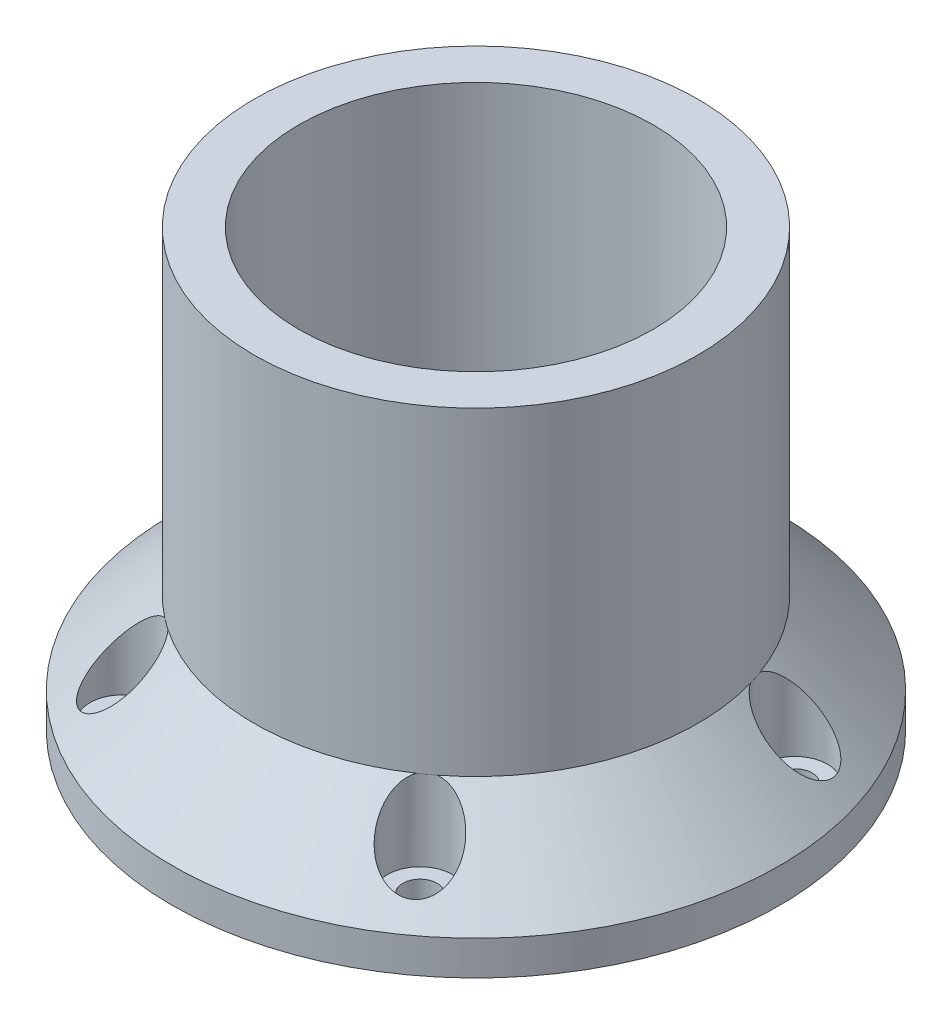
SolidWorks part; units mm, degrees
ref_plane "Front Plane" through (0, 0, 0) normal (0, 0, 1) x (1, 0, 0)
ref_plane "Top Plane" through (0, 0, 0) normal (0, 1, 0) x (1, 0, 0)
ref_plane "Right Plane" through (0, 0, 0) normal (1, 0, 0) x (0, 0, -1)
sketch "Sketch1" plane through (0, 0, 0) normal (0, 1, 0) x (1, 0, 0)
  circle A0 centre (0, 0) radius 25 construction
  circle A1 centre (0, 25) radius 1.7
  circle A2 centre (23.7764, 7.7254) radius 1.7
  circle A3 centre (14.6946, -20.2254) radius 1.7
  circle A4 centre (-14.6946, -20.2254) radius 1.7
  circle A5 centre (-23.7764, 7.7254) radius 1.7
  circle A6 centre (0, 0) radius 30
  circle A7 centre (0, 0) radius 17.5
  point P16 (0, 0)
  dimension "D1" = 50
  dimension "D2" = 3.4
  dimension "D4" = 60
  dimension "D5" = 35
  dimension "D3" = 5
extrude "Boss-Extrude1" add sketch "Sketch1" along normal blind 3
sketch "Sketch2" plane through (0, 3, 0) normal (0, 1, 0) x (1, 0, 0)
  circle A0 centre (0, 25) radius 3.1 construction
  circle A1 centre (0, 0) radius 21.9
  circle A2 centre (0, 0) radius 17.5 construction
  circle A3 centre (0, 0) radius 17.5
  dimension "D1" = 6.2
extrude "Boss-Extrude2" add sketch "Sketch2" along normal blind 40
chamfer "Chamfer1" distance 8.5 angle 45 1 edges at (0, 3, 21.9)
ref_plane "Plane1" through (0, 11.5, 0) normal (0, -1, 0) x (-1, 0, 0)
sketch "Sketch3" plane through (0, 11.5, 0) normal (0, -1, 0) x (-1, 0, 0)
  circle A0 centre (0, 25) radius 1.7 construction
  circle A1 centre (0, 25) radius 1.7
  circle A2 centre (0, 25) radius 3.2
  circle A3 centre (23.7764, 7.7254) radius 3.2
  circle A4 centre (14.6946, -20.2254) radius 3.2
  circle A5 centre (-14.6946, -20.2254) radius 3.2
  circle A6 centre (-23.7764, 7.7254) radius 3.2
  circle A7 centre (-23.7764, 7.7254) radius 1.7 construction
  circle A8 centre (-14.6946, -20.2254) radius 1.7 construction
  circle A9 centre (14.6946, -20.2254) radius 1.7 construction
  circle A10 centre (23.7764, 7.7254) radius 1.7 construction
  circle A11 centre (-23.7764, 7.7254) radius 1.7
  circle A12 centre (-14.6946, -20.2254) radius 1.7
  circle A13 centre (14.6946, -20.2254) radius 1.7
  circle A14 centre (23.7764, 7.7254) radius 1.7
  point P15 (0, 0)
  dimension "D2" = 5
  dimension "D1" = 1.5
extrude "Cut-Extrude3" cut sketch "Sketch3" along normal blind 8
